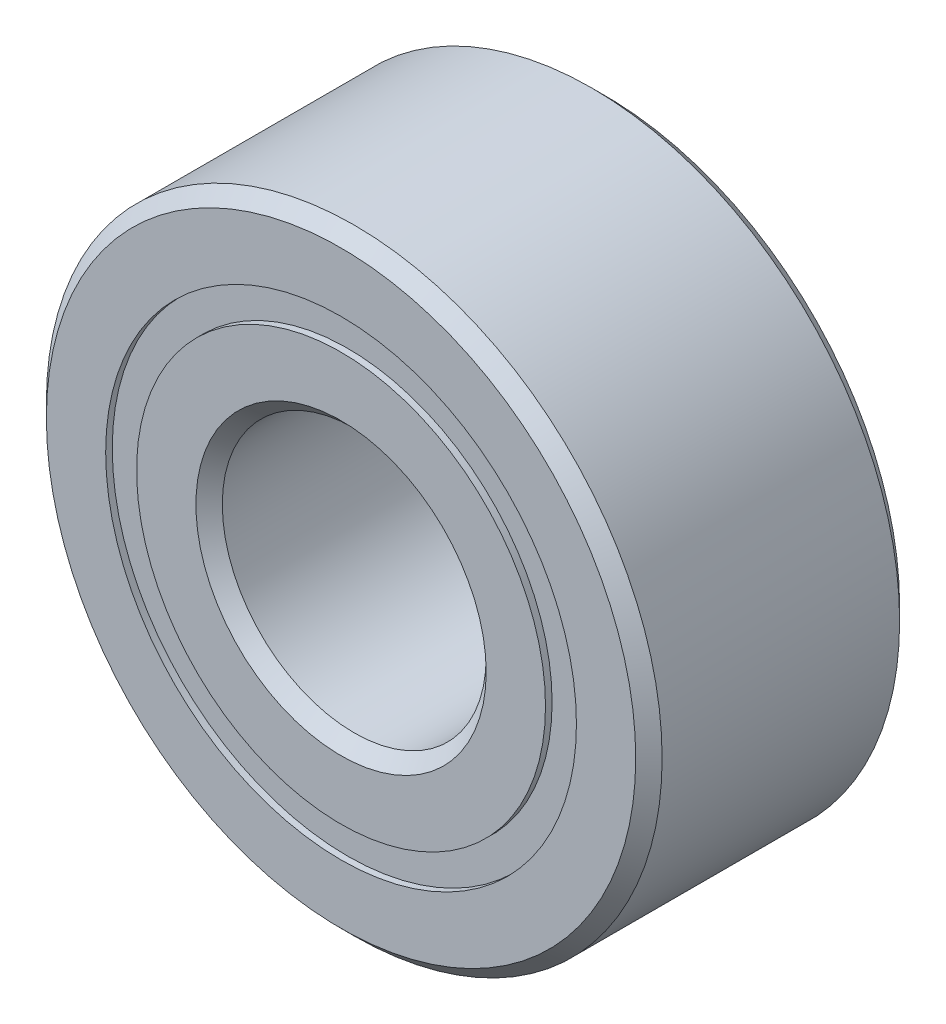
SolidWorks part; units mm, degrees
ref_plane "Front Plane" through (0, 0, 0) normal (0, 0, 1) x (1, 0, 0)
ref_plane "Top Plane" through (0, 0, 0) normal (0, 1, 0) x (1, 0, 0)
ref_plane "Right Plane" through (0, 0, 0) normal (1, 0, 0) x (0, 0, -1)
sketch "Sketch1" plane through (0, 0, 0) normal (1, 0, 0) x (0, 0, -1)
  line L0 (-1.5, 0) -> (1.5, 0) construction
  line L1 (0, 3.5) -> (0, -3.5) construction
  line L2 (1.35, 3.5) -> (-1.35, 3.5)
  line L3 (-1.35, 3.5) -> (-1.5, 3.35)
  line L4 (-1.5, 3.35) -> (-1.5, 2.6758)
  line L5 (-1.5, 2.6758) -> (-0.6667, 2.6758)
  line L6 (1.5, 2.6758) -> (0.6667, 2.6758)
  line L7 (1.5, 3.35) -> (1.5, 2.6758)
  line L8 (1.35, 3.5) -> (1.5, 3.35)
  line L9 (0, 3.5) -> (0, 2.5) construction
  line L10 (0, 2.5) -> (0, 1.5) construction
  arc A0 (-0.6667, 2.6758) -> (0.6667, 2.6758) centre (0, 2.5) cw
  point P14 (0, 1.5)
  dimension "Width" = 3
  dimension "OD" = 7
  dimension "D1" = 45
  dimension "D2" = 0.15
  dimension "Shaft Dia" = 3
  dimension "D3" = 1.3333
  dimension "D4" = 0.1758
revolve "Revolve1" add sketch "Sketch1" angle 360 about L0
sketch "Sketch3" plane through (0, 0, 0) normal (1, 0, 0) x (0, 0, -1)
  line L0 (-1.5, 2.3242) -> (-0.6667, 2.3242)
  line L1 (0, 3.5) -> (0, -3.5) construction
  line L2 (-1.5, 3.35) -> (-1.5, 2.6758) construction
  line L3 (-1.5, 2.3242) -> (-1.5, 1.65)
  line L4 (-1.35, 3.5) -> (-1.5, 3.35) construction
  line L5 (-1.5, 1.65) -> (-1.35, 1.5)
  line L6 (-1.35, 1.5) -> (1.35, 1.5)
  line L7 (1.35, 3.5) -> (1.35, -3.5) construction
  line L8 (1.35, 1.5) -> (1.5, 1.65)
  line L9 (1.5, -3.35) -> (1.5, 3.35) construction
  line L10 (1.5, 1.65) -> (1.5, 2.3242)
  line L11 (1.5, 2.3242) -> (0.6667, 2.3242)
  line L13 (1.35, 3.5) -> (1.5, 3.35) construction
  arc A0 (0.6667, 2.6758) -> (-0.6667, 2.6758) centre (0, 2.5) ccw construction
  arc A1 (0.6667, 2.3242) -> (-0.6667, 2.3242) centre (0, 2.5) cw
revolve "Revolve3" add sketch "Sketch3" angle 360 about L0
sketch "Sketch4" plane through (0, 0, 0) normal (1, 0, 0) x (0, 0, -1)
  line L0 (-0.6895, 2.5) -> (0.6895, 2.5)
  arc A2 (-0.6895, 2.5) -> (0.6895, 2.5) centre (0, 2.5) cw
  arc A3 (0.6667, 2.6758) -> (-0.6667, 2.6758) centre (0, 2.5) ccw construction
revolve "Revolve4" add sketch "Sketch4" angle 360 about L0
ref_axis "Axis1" through (0, 0, -1.5) along (0, 0, 1)
pattern_circular "CirPattern1" count 12 every 30 about axis through (0, 0, -1.5) along (0, 0, 1) of bodies 104
sketch "Sketch5" plane through (0, 0, 0) normal (1, 0, 0) x (0, 0, -1)
  line L0 (-1.5, 2.6758) -> (-0.6667, 2.6758) construction
  line L1 (-1.425, 2.6758) -> (-0.6895, 2.6758)
  line L2 (-1.425, 2.6758) -> (-1.425, 2.3242)
  line L3 (-1.425, 2.3242) -> (-0.6895, 2.3242)
  line L4 (-0.6895, 2.6758) -> (-0.6895, 2.3242)
  line L5 (-1.5, 2.3242) -> (-0.6667, 2.3242) construction
  line L6 (1.5, 2.6758) -> (0.6667, 2.6758) construction
  line L7 (1.425, 2.6758) -> (0.6895, 2.6758)
  line L8 (1.425, 2.6758) -> (1.425, 2.3242)
  line L9 (1.425, 2.3242) -> (0.6895, 2.3242)
  line L10 (0.6895, 2.6758) -> (0.6895, 2.3242)
  line L11 (1.5, 2.3242) -> (0.6667, 2.3242) construction
  line L12 (-1.35, 3.5) -> (-1.5, 3.35) construction
  point P18 (-1.425, 3.425)
revolve "Revolve5" add sketch "Sketch5" angle 360 about L0
sketch "Sketch6" plane through (0, 0, 0) normal (1, 0, 0) x (0, 0, -1)
  line L0 (1.5, 0) -> (-1.5, 0) construction
  line L1 (1.5, 2.6758) -> (0.4, 2.6758)
  line L2 (1.5, 2.6758) -> (1.5, 9.5)
  line L3 (1.5, 9.5) -> (0.4, 9.5)
  line L4 (0.4, 2.6758) -> (0.4, 9.5)
  dimension "Th" = 1.1
  dimension "Flange OD" = 19
revolve "Revolve6" [suppressed] add sketch "Sketch6" angle 360 about L0
equation "\"D2@Sketch1\" = \"Width@Sketch1\"*.05"
equation "\"D3@Sketch1\" = \"Width@Sketch1\"/2.25"
equation "\"D4@Sketch1\" = (((\"OD@Sketch1\"-\"Width@Sketch1\")/2)/3.25)/3.5"
equation "\"D2@CirPattern1\" = 360/\"Balls@CirPattern1\""
